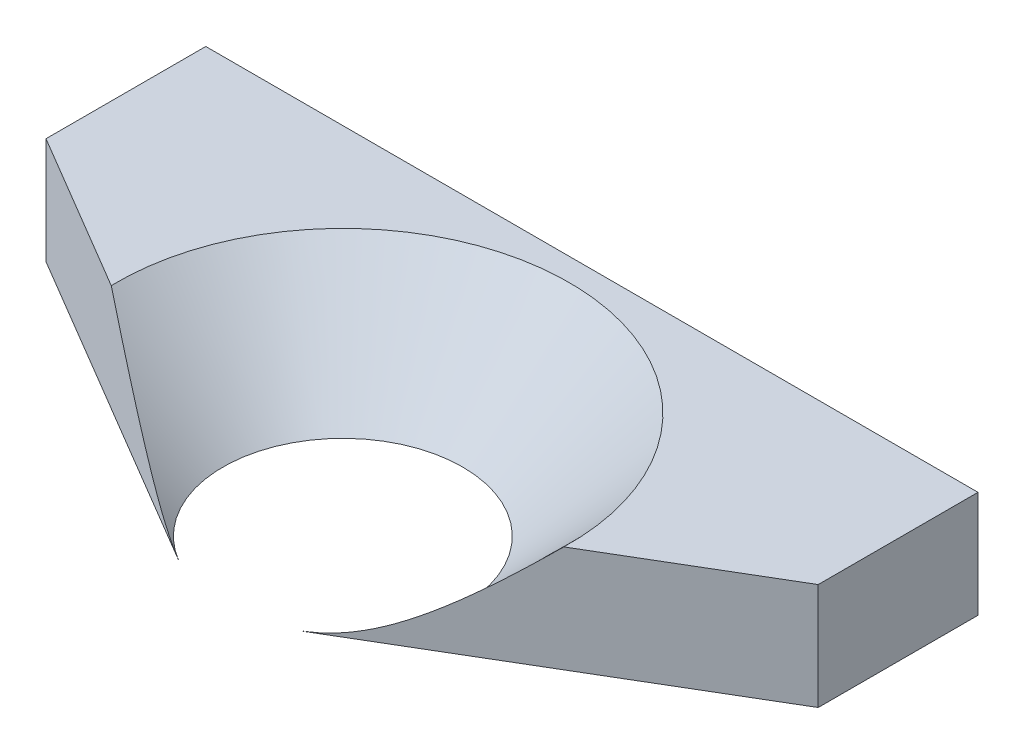
SolidWorks part; units mm, degrees
ref_plane "Płaszczyzna przednia" through (0, 0, 0) normal (0, 0, 1) x (1, 0, 0)
ref_plane "Płaszczyzna górna" through (0, 0, 0) normal (0, 1, 0) x (1, 0, 0)
ref_plane "Płaszczyzna prawa" through (0, 0, 0) normal (1, 0, 0) x (0, 0, -1)
sketch "Szkic1" plane through (0, 0, 0) normal (0, 1, 0) x (1, 0, 0)
  line L1 (-72.5, 15) -> (72.5, 15)
  line L2 (-72.5, 15) -> (-72.5, -15)
  line L3 (-72.5, -15) -> (72.5, -15)
  line L4 (72.5, 15) -> (72.5, -15)
  line L5 (-72.5, 15) -> (72.5, -15) construction
  line L6 (-72.5, -15) -> (72.5, 15) construction
  point P0 (0, 0)
  dimension "D1" = 30
  dimension "D2" = 145
extrude "Dodanie-wyciągnięcie1" add sketch "Szkic1" along normal blind 20
sketch "Szkic2" plane through (0, 20, 0) normal (0, 1, 0) x (1, 0, 0)
  line L12 (62.5, -15) -> (62.5, 174)
  line L13 (62.5, 174) -> (27.5, 174)
  line L14 (27.5, 174) -> (27.5, -15)
  line L15 (27.5, -15) -> (62.5, -15)
  line L16 (17.5, -15) -> (17.5, 174)
  line L17 (17.5, 174) -> (-17.5, 174)
  line L18 (-17.5, 174) -> (-17.5, -15)
  line L19 (-17.5, -15) -> (17.5, -15)
  line L20 (-27.5, -15) -> (-27.5, 174)
  line L21 (-27.5, 174) -> (-62.5, 174)
  line L22 (-62.5, 174) -> (-62.5, -15)
  line L23 (-62.5, -15) -> (-27.5, -15)
  line L24 (-72.5, 13) -> (72.5, 13)
  line L25 (-72.5, 15) -> (-72.5, -15) construction
  line L26 (72.5, -15) -> (72.5, 15) construction
  line L27 (72.5, 15) -> (-72.5, 15) construction
  line M13 (-72.5, -15) -> (72.5, -15)
  dimension "D1" = 2
extrude "Wytnij-wyciągnięcie1" cut sketch "Szkic2" against normal blind 24 contours L24 L22 L20 M13 | L24 L18 L16 M13 | L24 L14 L12 M13 region at (45, 20, 1) region at (0, 20, 1) region at (-45, 20, 1)
sketch "Szkic4" plane through (0, 20, 0) normal (0, 1, 0) x (1, 0, 0)
  line L0 (0, 15) -> (0, -31.7641) construction
  line L1 (72.5, 15) -> (-72.5, 15) construction
  line L2 (-72.5, -15) -> (-11.46, -51.1269)
  line L3 (-72.5, 15) -> (-72.5, -15) construction
  line L4 (-72.5, -15) -> (-62.5, -15) construction
  line L5 (-72.5, -15) -> (-72.5, 15)
  line L6 (-72.5, 15) -> (72.5, 15)
  line L7 (72.5, 15) -> (72.5, -15)
  line L9 (62.5, -15) -> (72.5, -15) construction
  line L11 (72.5, -15) -> (11.46, -51.1269)
  arc A0 (-11.46, -51.1269) -> (11.46, -51.1269) centre (0, -31.7641) ccw
  dimension "D1" = 45
extrude "Dodanie-wyciągnięcie3" add sketch "Szkic4" against normal up to vertex (20 mm away) up to point (-72.5, 0, 15)
sketch "Szkic7" plane through (0, 0, 0) normal (0, -1, 0) x (1, 0, 0)
  circle A0 centre (0, 31.7641) radius 22.5
  arc A1 (11.46, 51.1269) -> (-11.46, 51.1269) centre (0, 31.7641) ccw construction
extrude "Wytnij-wyciągnięcie2" cut sketch "Szkic7" against normal blind 24 draft 45 contours A0 draft outward yes
sketch "Szkic10" plane through (0, 20, 0) normal (0, 1, 0) x (1, 0, 0)
  line L0 (-45, 0) -> (0, -31)
  line L4 (-45, -15) -> (-45, 0)
  line L8 (-27.5, -15) -> (-27.5, 174)
  line L9 (-27.5, 174) -> (-62.5, 174)
  line L10 (-62.5, 174) -> (-62.5, -15)
  line L11 (-62.5, -15) -> (-27.5, -15)
ref_plane "Płaszczyzna2" through (-14.6138, 0.3025, 21.2136) normal (0.5673, -0.0117, -0.8235) x (0.8235, 0, 0.5673)
ref_plane "Płaszczyzna3" through (-14.6138, 0.3025, 21.2136) normal (0.5673, -0.0117, -0.8235) x (0.8235, 0, 0.5673)
